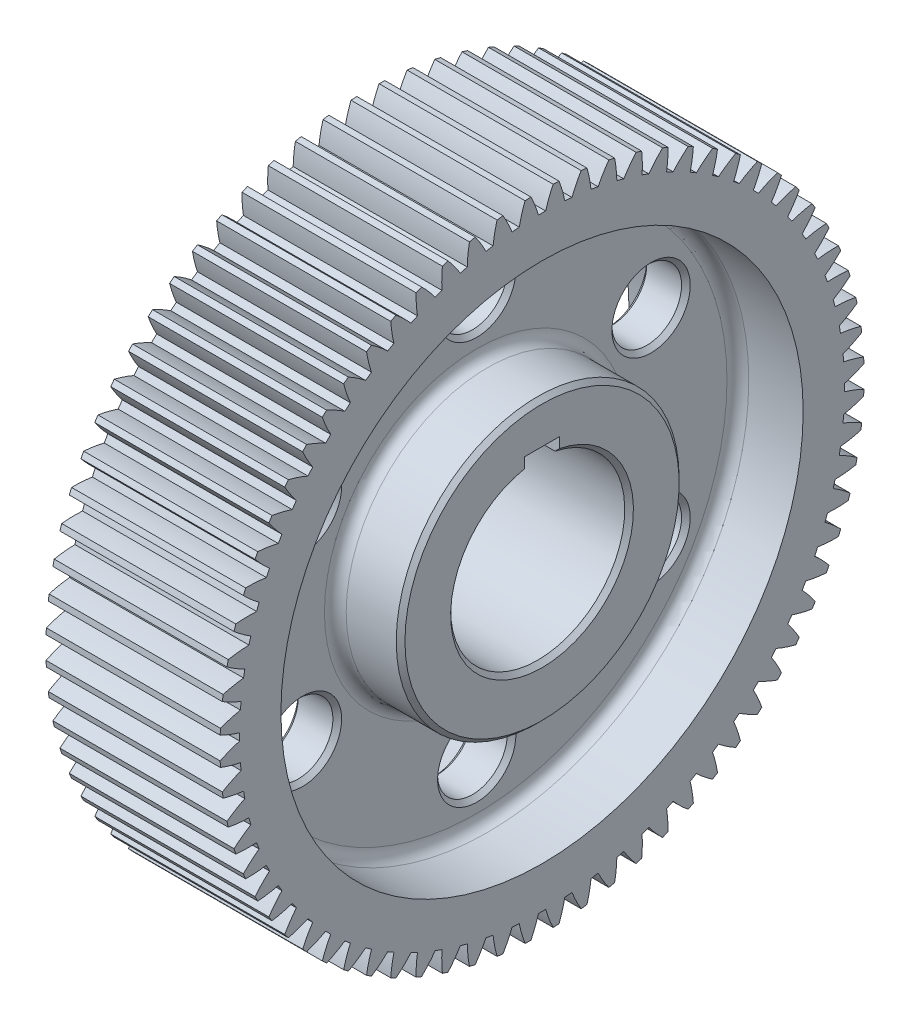
SolidWorks part; units mm, degrees
ref_plane "Plane1" through (0, 0, 0) normal (0, 0, 1) x (1, 0, 0)
ref_plane "Plane2" through (0, 0, 0) normal (0, 1, 0) x (1, 0, 0)
ref_plane "Plane3" through (0, 0, 0) normal (1, 0, 0) x (0, 0, -1)
other "Configuration Table"
sketch "HoldingSke" plane through (0, 0, 0) normal (0, 1, 0) x (1, 0, 0)
  line L0 (0, 0) -> (0.0773, -0.2378)
  line L1 (-15, 0) -> (100, 0) construction
  line L2 (0, 0) -> (-2.1039, 2.3779)
  line L3 (0, 0) -> (-11.863, 4.5341)
  line L4 (0, 0) -> (2.6687, 8.2133)
  line L5 (0, 0) -> (-46.8476, -17.4728)
  line L6 (0, 0) -> (-66.317, -44.7443)
  line L7 (-2.1039, 2.3779) -> (15.1161, 80.5027)
  line L8 (-76.2, 54.61) -> (-70.8, 54.61)
  line L9 (-71.009, 38.7566) -> (-53.1078, 45.2721)
  line L10 (-76.2, 71.12) -> (104.1128, 71.12)
  line L11 (0, 0) -> (-80, 0)
  line L12 (-76.2, 101.6) -> (-76.073, 101.6)
  line L13 (24.9733, 27.94) -> (52.9518, 28.4284)
  line L14 (24.9733, 27.94) -> (24.9743, 27.94)
  line L15 (24.9733, 27.94) -> (100.4006, 29.5858)
  line L16 (-63.627, -4) -> (-12.827, -4)
  circle A0 centre (0, 0) radius 40
  circle A1 centre (0, 0) radius 37.5
  circle A2 centre (0, 0) radius 37.5
  circle A3 centre (0, 0) radius 40
  dimension "MHD" = 75
  dimension "Hub_dia" = 75
  dimension "Bore" = 80
  dimension "MBD" = 80
  dimension "Num_teeth" = 72
  dimension "Pitch_radius" = 180.3128
  dimension "Pitch" = 0.25
  dimension "Width" = 80
  dimension "Overall_len" = 50
  dimension "Show_teeth" = 72
  dimension "Thickness" = 80
  dimension "OAL" = 80.0001
  dimension "T_dim" = 5.4
  dimension "Ap" = 20
  dimension "H" = 19.05
  dimension "Backlash" = 0.127
  dimension "Addendum_fac" = 1
  dimension "Dedendum_fac" = 1.25
  dimension "Clearance_fac" = 0.25
  dimension "Dedendum_add" = 0.001
  dimension "Module" = 4
sketch "BasProSke" plane through (0, 0, 0) normal (0, 1, 0) x (1, 0, 0)
  line L0 (-10, 0) -> (60, 0) construction
  line L1 (0, 0) -> (0, 148)
  line L2 (0, 0) -> (80, 0)
  line L3 (80, 0) -> (80, 148)
  line L4 (80, 148) -> (0, 148)
  dimension "Diameter" = 296
  dimension "Thickness" = 80
revolve "Base-Revolve" add sketch "BasProSke" angle 360 about L0
sketch "TooCutSke" plane through (0, 0, 0) normal (1, 0, 0) x (0, 0, -1)
  line L1 (0, 0) -> (0, 107) construction
  line L2 (0, 0) -> (-3.3636, 143.9607) construction
  line L3 (0, 0) -> (-12.5598, 287.6668) construction
  line L4 (-3.3636, 143.9607) -> (-6.2799, 143.8334) construction
  arc A0 (1.6538, 138.9892) -> (-1.6538, 138.9892) centre (0, 0) ccw
  arc A1 (5.1137, 147.937) -> (-5.1137, 147.937) centre (0, 0) ccw
  circle A2 centre (0, 0) radius 144 construction
  circle A3 centre (0, 0) radius 135.3157 construction
  arc A4 (-1.6538, 138.9892) -> (-5.1137, 147.937) centre (-56.9206, 122.7615) ccw
  arc A5 (5.1137, 147.937) -> (1.6538, 138.9892) centre (56.9206, 122.7615) ccw
  dimension "Root_dia" = 277.998
  dimension "Overcut_dia" = 296.0508
  dimension "Pitch_dia" = 288
  dimension "Base_dia" = 270.6315
  dimension "Flank_rad" = 57.6
  dimension "Half_ang" = 2.5
  dimension "Half_CT" = 2.9191
extrude "ToothCut" cut sketch "TooCutSke" along normal through all
fillet "Breaks" [suppressed] radius 0.08 tangent propagation no
fillet "RootFillets" [suppressed] radius 1.001
pattern_circular "TeethCuts" count 72 every 5 about axis through (-10, 0, 0) along (1, 0, 0) of "ToothCut", "RootFillets", "Breaks"
sketch "HubNeaOneSke" plane through (0, 0, 0) normal (-1, 0, 0) x (0, 0, 1)
  circle A0 centre (0, 0) radius 37.5
  dimension "Diameter" = 75
extrude "HubNearOne" [suppressed] add sketch "HubNeaOneSke" along normal blind 38.0001
sketch "HubNeaBotSke" plane through (0, 0, 0) normal (-1, 0, 0) x (0, 0, 1)
  circle A0 centre (0, 0) radius 37.5
  dimension "Diameter" = 75
extrude "HubNearBoth" [suppressed] add sketch "HubNeaBotSke" along normal blind 19
ref_plane "FarPln" through (80, 0, 0) normal (1, 0, 0) x (0, 0, -1)
sketch "HubFarSke" plane through (80, 0, 0) normal (1, 0, 0) x (0, 0, -1)
  circle A0 centre (0, 0) radius 37.5
  dimension "Diameter" = 75
extrude "HubFar" [suppressed] add sketch "HubFarSke" along normal blind 19
sketch "BorSke" plane through (0, 0, 0) normal (1, 0, 0) x (0, 0, -1)
  circle A0 centre (0, 0) radius 40
  dimension "Diameter" = 80
extrude "Bore" cut sketch "BorSke" along normal mid plane 160.0001
sketch "KeySke" plane through (0, 0, 0) normal (1, 0, 0) x (0, 0, -1)
  line L0 (-11, 0) -> (-11, 45.4)
  line L1 (-11, 45.4) -> (11, 45.4)
  line L2 (11, 45.4) -> (11, 0)
  line L3 (0, 0) -> (0, 34) construction
  line L4 (-11, 0) -> (11, 0)
  dimension "Offset" = 45.4
  dimension "Width" = 22
extrude "Keyway" [suppressed] cut sketch "KeySke" along normal mid plane 160.0001
pattern_circular "Keyway2" [suppressed] count 2 every 90 about axis through (-10, 0, 0) along (1, 0, 0) reverse direction yes
sketch "Sketch1" plane through (80, 0, 0) normal (1, 0, 0) x (0, 0, -1)
  circle A0 centre (0, 0) radius 65
  circle A1 centre (0, 0) radius 120
  dimension "D1" = 130
  dimension "D2" = 240
extrude "Cut-Extrude1" cut sketch "Sketch1" against normal blind 30
extrude "Cut-Extrude2" cut sketch "Sketch1<2>" along normal blind 30 from surface starting at face at (0, 0, -40)
sketch "Sketch1<2>" plane through (80, 0, 0) normal (1, 0, 0) x (0, 0, -1) same geometry as "Sketch1"
sketch "Sketch2" plane through (80, 0, 0) normal (1, 0, 0) x (0, 0, -1)
  circle A0 centre (0, 0) radius 92.5
  circle A1 centre (0, 92.5) radius 16
  dimension "D1" = 32
  dimension "D2" = 185
extrude "Cut-Extrude3" cut sketch "Sketch2" against normal through all contours A0 A1 | A0 A1 region at (80, 85.4663, 0) region at (80, 99.0353, 0)
pattern_circular "CirPattern1" count 6 over 360 about axis through (50, 0, 0) along (1, 0, 0) of "Cut-Extrude3" reverse direction yes
sketch "Sketch3" plane through (80, 0, 0) normal (1, 0, 0) x (0, 0, -1)
  line L1 (-8, 34) -> (8, 34)
  line L2 (-8, 34) -> (-8, 46)
  line L3 (-8, 46) -> (8, 46)
  line L4 (8, 34) -> (8, 46)
  line L5 (-8, 34) -> (8, 46) construction
  line L6 (-8, 46) -> (8, 34) construction
  circle A0 centre (0, 0) radius 40 construction
  point P0 (0, 40)
  dimension "D1" = 16
  dimension "D2" = 12
extrude "Cut-Extrude4" cut sketch "Sketch3" against normal through all
fillet "Fillet1" radius 5 4 edges at (30, 0, -65) (30, 0, -120) (50, 0, -65) (50, 0, -120)
chamfer "Chamfer1" distance 2 angle 45 16 edges at (30, -46.25, 64.1073) (50, -46.25, 64.1073) (30, -92.5, -16) (50, -92.5, -16) (30, -46.25, -96.1073) (50, -46.25, -96.1073) (30, 46.25, -96.1073) (50, 46.25, -96.1073) (30, 92.5, -16) (50, 92.5, -16) (30, 46.25, 64.1073) (50, 46.25, 64.1073) (0, -40, 0) (0, 0, -65) (80, -40, 0) (80, 0, -65)
